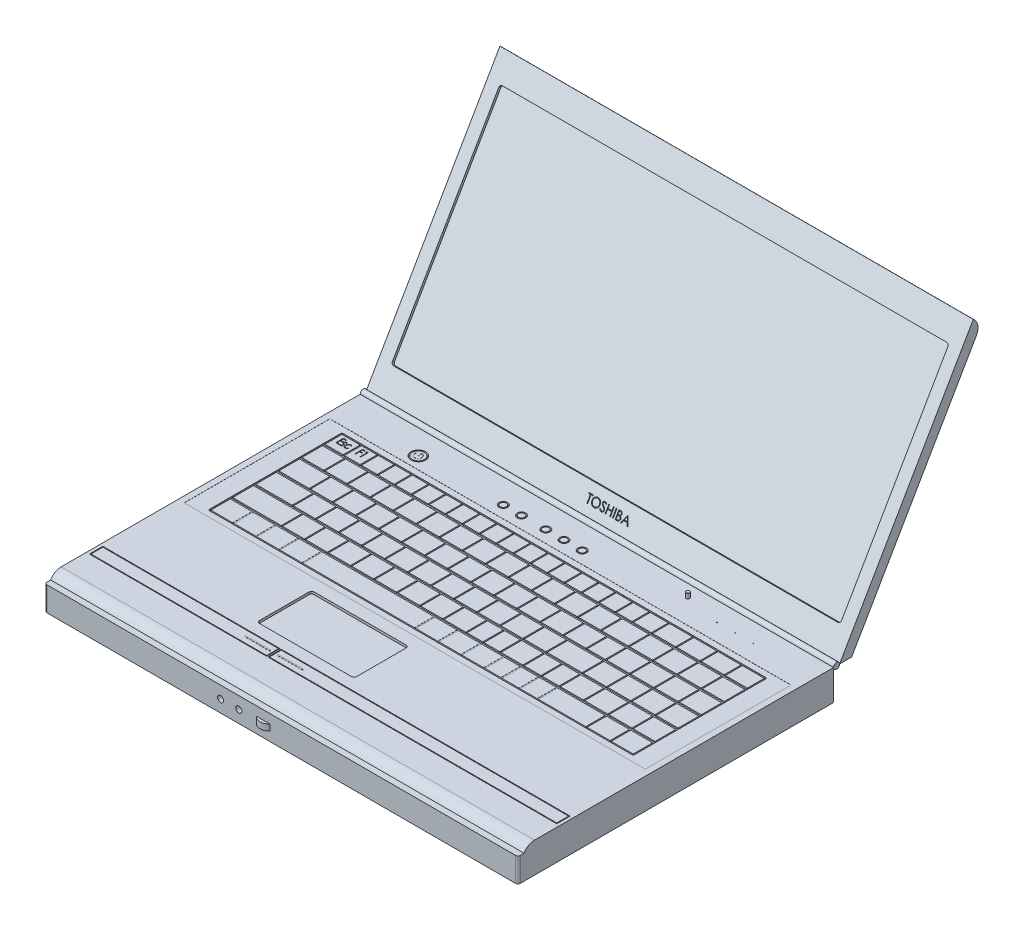
SolidWorks part; units mm, degrees
ref_plane "Front" through (0, 0, 0) normal (0, 0, 1) x (1, 0, 0)
ref_plane "Top" through (0, 0, 0) normal (0, 1, 0) x (1, 0, 0)
ref_plane "Right" through (0, 0, 0) normal (1, 0, 0) x (0, 0, -1)
sketch "Sketch1" plane through (0, 0, 0) normal (0, 1, 0) x (1, 0, 0)
  line L1 (-195, -130) -> (195, -130)
  line L2 (-195, -130) -> (-195, 130)
  line L3 (-195, 130) -> (195, 130)
  line L4 (195, -130) -> (195, 130)
  line L5 (-195, -130) -> (195, 130) construction
  line L6 (-195, 130) -> (195, -130) construction
  point P0 (0, 0)
  dimension "D1" = 390
  dimension "D2" = 260
extrude "Extrude1" add sketch "Sketch1" along normal blind 25
sketch "Sketch2" plane through (195, 0, 0) normal (1, 0, 0) x (0, 0, -1)
  line L0 (135, 25) -> (245.1819, 215.8407)
  line L1 (245.1819, 215.8407) -> (255.1819, 215.8407)
  line L2 (255.1819, 215.8407) -> (145, 25)
  line L3 (145, 25) -> (135, 25)
  line L4 (-130, 25) -> (130, 25) construction
  dimension "D1" = 5
  dimension "D2" = 120
  dimension "D3" = 10
extrude "Extrude2" add sketch "Sketch2" against normal through all separate body
sketch "Sketch3" plane through (195, 0, 0) normal (1, 0, 0) x (0, 0, -1)
  line L0 (122.4808, 25) -> (146.9706, 25) construction
  line L1 (-130, 25) -> (130, 25) construction
  line L2 (130, 25) -> (130, 0) construction
  circle A0 centre (132.5, 25) radius 2.5
  dimension "D1" = 5
extrude "Extrude3" add sketch "Sketch3" against normal through all separate body
sketch "Sketch4" plane through (0, -52.2067, -90.4247) normal (0, 0.5, 0.866) x (1, 0, 0)
  line L0 (-195, 309.5145) -> (-195, 89.1506) construction
  line L1 (-185, 110.4006) -> (185, 110.4006)
  line L2 (-185, 110.4006) -> (-185, 289.5145)
  line L3 (-185, 289.5145) -> (185, 289.5145)
  line L4 (185, 110.4006) -> (185, 289.5145)
  line L5 (-185, 110.4006) -> (185, 289.5145) construction
  line L6 (-185, 289.5145) -> (185, 110.4006) construction
  line L7 (195, 309.5145) -> (195, 89.1506) construction
  line L8 (-195, 309.5145) -> (195, 309.5145) construction
  line L9 (195, 90.4006) -> (-195, 90.4006) construction
  point P0 (0, 199.9576)
  dimension "D1" = 10
  dimension "D2" = 10
  dimension "D3" = 20
  dimension "D4" = 20
extrude "Extrude4" cut sketch "Sketch4" against normal blind 2
fillet "Fillet1" radius 2 4 edges at (185, 198.0202, -236.048) (185, 42.903, -146.491) (-185, 42.903, -146.491) (-185, 198.0202, -236.048)
fillet "Fillet2" radius 10 1 edges at (0, 215.8407, -255.1819)
sketch "Sketch5" plane through (0, 25, 0) normal (0, 1, 0) x (1, 0, 0)
  line L0 (195, -130) -> (195, 130) construction
  line L1 (-195, -130) -> (195, -130)
  line L2 (-195, -130) -> (-195, -125)
  line L3 (-195, -125) -> (195, -125)
  line L4 (195, -130) -> (195, -125)
  dimension "D1" = 5
extrude "Extrude5" cut sketch "Sketch5" against normal blind 5
fillet "Fillet3" radius 10 1 edges at (0, 25, 125)
fillet "Fillet4" radius 2 2 edges at (195, 10, 130) (-195, 10, 130)
sketch "Sketch6" plane through (0, 25, 0) normal (0, 1, 0) x (1, 0, 0)
  line L0 (-195, 130) -> (195, 130) construction
  line L1 (-75, -30) -> (5, -30)
  line L2 (-75, -30) -> (-75, -75)
  line L3 (-75, -75) -> (5, -75)
  line L4 (5, -30) -> (5, -75)
  line L5 (-195, 130) -> (-195, -116.3397) construction
  line L6 (-193, -130) -> (193, -130) construction
  circle A0 centre (-127.0409, 110) radius 6
  circle A1 centre (-127.0409, 110) radius 5
  circle A2 centre (-57.0409, 110) radius 3.5
  circle A3 centre (-57.0409, 110) radius 2.5
  circle A4 centre (-42.0409, 110) radius 3.5
  circle A5 centre (-42.0409, 110) radius 2.5
  circle A6 centre (-22.0409, 110) radius 3.5
  circle A7 centre (-22.0409, 110) radius 2.5
  circle A8 centre (-7.0409, 110) radius 3.5
  circle A9 centre (-7.0409, 110) radius 2.5
  circle A10 centre (7.9591, 110) radius 3.5
  circle A11 centre (7.9591, 110) radius 2.5
  dimension "D2" = 12
  dimension "D3" = 10
  dimension "D8" = 7
  dimension "D9" = 5
  dimension "D10" = 7
  dimension "D11" = 5
  dimension "D12" = 7
  dimension "D13" = 5
  dimension "D14" = 5
  dimension "D15" = 7
  dimension "D21" = 5
  dimension "D22" = 7
  dimension "D1" = 20
  dimension "D4" = 80
  dimension "D5" = 45
  dimension "D6" = 120
  dimension "D7" = 55
  dimension "D16" = 15
  dimension "D17" = 70
  dimension "D18" = 20
  dimension "D19" = 15
  dimension "D20" = 15
extrude "Extrude6" cut sketch "Sketch6" against normal blind 2
fillet "Fillet5" radius 2 4 edges at (5, 24, 30) (5, 24, 75) (-75, 24, 75) (-75, 24, 30)
sketch "Sketch8" plane through (0, 0, 130) normal (0, 0, 1) x (1, 0, 0)
  line L0 (-195, 0) -> (-195, 20) construction
  line L1 (-207.7397, 10) -> (97.3758, 10) construction
  line L2 (-193, 0) -> (193, 0) construction
  line L3 (-193, 20) -> (193, 20) construction
  circle A0 centre (-50, 10) radius 2.5
  circle A1 centre (-35, 10) radius 2.5
  dimension "D1" = 5
  dimension "D2" = 5
  dimension "D3" = 145
  dimension "D4" = 15
extrude "Extrude7" cut sketch "Sketch8" against normal blind 10
sketch "Sketch9" plane through (0, 25, 0) normal (0, 1, 0) x (1, 0, 0)
  line L0 (-195, 130) -> (195, 130) construction
  line L1 (195, -116.3397) -> (195, 130) construction
  circle A0 centre (85, 120) radius 1.5
  dimension "D1" = 3
  dimension "D2" = 10
  dimension "D3" = 110
extrude "Extrude8" add sketch "Sketch9" along normal blind 4
ref_plane "Plane1" through (0, 10, 0) normal (0, 1, 0) x (-1, 0, 0)
sketch "Sketch10" plane through (0, 10, 0) normal (0, 1, 0) x (-1, 0, 0)
  line L0 (-195, 125) -> (195, 125) construction
  line L1 (-195, 116.3397) -> (-195, -130) construction
  circle A0 centre (15, 125) radius 7.5
  dimension "D1" = 15
  dimension "D2" = 210
extrude "Extrude9" add sketch "Sketch10" along normal blind 2.5 and the other way blind 2.5
sketch "Sketch11" plane through (0, 25, 0) normal (0, 1, 0) x (1, 0, 0)
  line L1 (-192, -85) -> (-47, -85)
  line L2 (-192, -85) -> (-192, -95)
  line L3 (-192, -95) -> (-47, -95)
  line L4 (-47, -85) -> (-47, -95)
  line L5 (195, -116.3397) -> (195, 130) construction
  line L6 (-45, -95) -> (192, -95)
  line L7 (-45, -95) -> (-45, -85)
  line L8 (-45, -85) -> (192, -85)
  line L9 (-195, 130) -> (-195, -116.3397) construction
  line L10 (192, -95) -> (192, -85)
  line L11 (-193, -130) -> (193, -130) construction
  dimension "D1" = 3
  dimension "D2" = 3
  dimension "D3" = 2
  dimension "D4" = 10
  dimension "D5" = 35
  dimension "D6" = 145
sketch "Sketch14" plane through (0, 25, 0) normal (0, 1, 0) x (-1, 0, 0)
  line L0 (192, 85) -> (47, 85) construction
  line L1 (192.5, 84.5) -> (46.5, 84.5)
  line L2 (192.5, 84.5) -> (192.5, 95.5)
  line L3 (192.5, 95.5) -> (46.5, 95.5)
  line L4 (46.5, 84.5) -> (46.5, 95.5)
  line L5 (45.5, 95.5) -> (-192.5, 95.5)
  line L6 (45.5, 95.5) -> (45.5, 84.5)
  line L7 (45.5, 84.5) -> (-192.5, 84.5)
  line L8 (-192.5, 95.5) -> (-192.5, 84.5)
  line L9 (192, 95) -> (47, 95) construction
  line L10 (192, 85) -> (192, 95) construction
  line L11 (47, 85) -> (47, 95) construction
  line L12 (45, 95) -> (45, 85) construction
  line L13 (45, 95) -> (-192, 95) construction
  line L14 (45, 85) -> (-192, 85) construction
  line L15 (-192, 95) -> (-192, 85) construction
  dimension "D1" = 0.5
  dimension "D2" = 0.5
  dimension "D3" = 0.5
  dimension "D4" = 0.5
  dimension "D5" = 0.5
  dimension "D6" = 0.5
  dimension "D7" = 0.5
  dimension "D8" = 0.5
extrude "Extrude12" cut sketch "Sketch14" against normal blind 2
extrude "Extrude13" add sketch "Sketch11" against normal blind 2
sketch "Sketch15" plane through (0, 25, 0) normal (0, 1, 0) x (1, 0, 0)
  line L0 (-69.5, -90) -> (-49.5, -90) construction
  line L1 (-69.5, -89.5) -> (-49.5, -89.5)
  line L2 (-69.5, -90.5) -> (-49.5, -90.5)
  line L3 (-42.5, -90) -> (-22.5, -90) construction
  line L4 (-42.5, -89.5) -> (-22.5, -89.5)
  line L5 (-42.5, -90.5) -> (-22.5, -90.5)
  line L6 (-47, -85) -> (-192, -85) construction
  line L7 (-192, -95) -> (-47, -95) construction
  line L9 (-47, -95) -> (-47, -85) construction
  line L10 (-45, -85) -> (-45, -95) construction
  arc A0 (-69.5, -89.5) -> (-69.5, -90.5) centre (-69.5, -90) ccw
  arc A1 (-49.5, -90.5) -> (-49.5, -89.5) centre (-49.5, -90) ccw
  arc A2 (-42.5, -89.5) -> (-42.5, -90.5) centre (-42.5, -90) ccw
  arc A3 (-22.5, -90.5) -> (-22.5, -89.5) centre (-22.5, -90) ccw
  point P2 (-59.5, -90)
  point P7 (-32.5, -90)
  point P20 (-45, -90)
  dimension "D1" = 1
  dimension "D2" = 1
  dimension "D3" = 20
  dimension "D4" = 20
  dimension "D5" = 2.5
  dimension "D6" = 2.5
extrude "Extrude14" add sketch "Sketch15" along normal blind 0.1
chamfer "Chamfer1" distance 0.1 angle 45 8 edges at (192, 25, 90) (73.5, 25, 95) (-45, 25, 90) (73.5, 25, 85) (-192, 25, 90) (-119.5, 25, 85) (-47, 25, 90) (-119.5, 25, 95)
sketch "Sketch16" plane through (0, 25, 0) normal (0, 1, 0) x (1, 0, 0)
  line L0 (-195, 130) -> (-195, -116.3397) construction
  line L1 (-190, 100) -> (190, 100)
  line L2 (-190, 100) -> (-190, -20)
  line L3 (-190, -20) -> (190, -20)
  line L4 (190, 100) -> (190, -20)
  line L5 (195, -116.3397) -> (195, 130) construction
  line L6 (195, 130) -> (-195, 130) construction
  dimension "D1" = 5
  dimension "D2" = 5
  dimension "D3" = 30
  dimension "D4" = 120
extrude "Extrude15" cut sketch "Sketch16" against normal blind 0.1
sketch "Sketch17" plane through (0, 25, 0) normal (0, 1, 0) x (1, 0, 0)
  line L0 (-127.1409, 103.668) -> (-127.1409, 116.8191) construction
  line L1 (-127.2409, 114) -> (-127.0409, 114)
  line L2 (-127.2409, 114) -> (-127.2409, 110)
  line L3 (-127.2409, 110) -> (-127.0409, 110)
  line L4 (-127.0409, 114) -> (-127.0409, 110)
  line L5 (-126.0409, 112.7911) -> (-126.0409, 112.5749)
  line L6 (-128.2409, 112.7911) -> (-128.2409, 112.5749)
  circle A0 centre (-127.0409, 110) radius 5 construction
  circle A3 centre (-127.0409, 110) radius 5 construction
  arc A4 (-126.0409, 112.7911) -> (-128.2409, 112.7911) centre (-127.1409, 110) cw
  arc A5 (-126.0409, 112.5749) -> (-128.2409, 112.5749) centre (-127.1409, 110) cw
  dimension "D7" = 2.8
  dimension "D8" = 3
  dimension "D1" = 4
  dimension "D2" = 0.2
  dimension "D3" = 0
  dimension "D4" = 0
  dimension "D5" = 1
  dimension "D6" = 1
extrude "Extrude16" cut sketch "Sketch17" against normal blind 0.1
sketch "Sketch18" plane through (0, 24.9, 0) normal (0, 1, 0) x (1, 0, 0)
  line L0 (190, 100) -> (-190, 100) construction
  line L1 (-175, 95) -> (175, 95)
  line L2 (-175, 95) -> (-175, -15)
  line L3 (-175, -15) -> (175, -15)
  line L4 (175, 95) -> (175, -15)
  line L5 (-190, 100) -> (-190, -20) construction
  line L6 (-190, -20) -> (190, -20) construction
  line L7 (190, -20) -> (190, 100) construction
  dimension "D1" = 5
  dimension "D2" = 15
  dimension "D3" = 5
  dimension "D4" = 15
extrude "Extrude17" cut sketch "Sketch18" against normal blind 0.1
fillet "Fillet6" radius 1 4 edges at (175, 24.85, -95) (175, 24.85, 15) (-175, 24.85, 15) (-175, 24.85, -95)
chamfer "Chamfer2" distance 0.1 angle 45 8 edges at (0, 24.9, 15) (174.7071, 24.9, 14.7071) (-174.7071, 24.9, 14.7071) (175, 24.9, -40) (-175, 24.9, -40) (174.7071, 24.9, -94.7071) (-174.7071, 24.9, -94.7071) (0, 24.9, -95)
sketch "Sketch19" plane through (0, 24.8, 0) normal (0, 1, 0) x (1, 0, 0)
  line L0 (-174.1, 61) -> (95.9, 61)
  line L2 (-174.1, 59) -> (95.9, 59)
  line L3 (95.9, 21) -> (-174.1, 21)
  line L5 (-174.1, 21) -> (-174.1, 23)
  line L6 (-174.1, 4) -> (-174.1, 2)
  line L7 (-174.1, 2) -> (95.9, 2)
  line L8 (-174, -15) -> (174, -15) construction
  line L9 (-174.1, 40) -> (-174.1, 42)
  line L10 (-174.1, 80) -> (-174.1, 78)
  line L11 (-174.1, 61) -> (-174.1, 59)
  line L12 (-175.1, -14) -> (-175.1, 94) construction
  line L19 (95.9, 61) -> (95.9, 59)
  line L20 (-174.1, 80) -> (95.9, 80)
  line L21 (-174.1, 78) -> (95.9, 78)
  line L22 (95.9, 80) -> (95.9, 78)
  line L35 (-174.1, 42) -> (95.9, 42)
  line L37 (-174.1, 40) -> (95.9, 40)
  line L38 (95.9, 42) -> (95.9, 40)
  line L39 (-174.1, 23) -> (95.9, 23)
  line L42 (95.9, 23) -> (95.9, 21)
  line L43 (-174.1, 4) -> (95.9, 4)
  line L46 (95.9, 4) -> (95.9, 2)
  dimension "D2" = 2
  dimension "D3" = 17
  dimension "D4" = 2
  dimension "D5" = 270
  dimension "D6" = 17
  dimension "D7" = 2
  dimension "D8" = 2
  dimension "D9" = 2
  dimension "D10" = 17
  dimension "D11" = 17
  dimension "D12" = 17
  dimension "D13" = 1
extrude "Extrude18" cut sketch "Sketch19" against normal blind 1
sketch "Sketch20" plane through (0, 24.8, 0) normal (0, 1, 0) x (-1, 0, 0)
  line L0 (175, -94) -> (175, 14)
  line L1 (174, -94) -> (175, -94)
  line L2 (174, -94) -> (174, 14)
  line L3 (175, 14) -> (174, 14)
extrude "Extrude19" cut sketch "Sketch20" against normal blind 1
sketch "Sketch23" plane through (0, 24.8, 0) normal (0, 1, 0) x (1, 0, 0)
  line L0 (-174, -14) -> (-174, -15)
  line L1 (-175, -14) -> (-174, -14)
  arc A0 (-174, -15) -> (-175, -14) centre (-174, -14) cw
extrude "Extrude24" cut sketch "Sketch23" against normal blind 1
sketch "Sketch25" plane through (0, 24.8, 0) normal (0, 1, 0) x (1, 0, 0)
  line L0 (-174, 94) -> (-174, 95)
  line L1 (174, 95) -> (-174, 95) construction
  line L2 (-175, 94) -> (-174, 94)
  arc A0 (-174, 95) -> (-175, 94) centre (-174, 94) ccw construction
  arc A1 (-174, 95) -> (-175, 94) centre (-174, 94) ccw
extrude "Extrude25" cut sketch "Sketch25" against normal blind 1
sketch "Sketch26" plane through (0, 24.8, 0) normal (0, 1, 0) x (-1, 0, 0)
  line L1 (174, -95) -> (-174, -95)
  line L2 (174, -95) -> (174, -94)
  line L3 (174, -94) -> (-174, -94)
  line L4 (-174, -95) -> (-174, -94)
extrude "Extrude26" cut sketch "Sketch26" against normal blind 1
sketch "Sketch27" plane through (0, 24.8, 0) normal (0, 1, 0) x (-1, 0, 0)
  line L0 (-174, -95) -> (-174, -94)
  line L1 (-174, -94) -> (-175, -94)
  arc A0 (-175, -94) -> (-174, -95) centre (-174, -94) ccw
extrude "Extrude27" cut sketch "Sketch27" against normal blind 1
sketch "Sketch28" plane through (0, 24.8, 0) normal (0, 1, 0) x (1, 0, 0)
  line L1 (175, 94) -> (174, 94)
  line L2 (175, 94) -> (175, -14)
  line L3 (175, -14) -> (174, -14)
  line L4 (174, 94) -> (174, -14)
extrude "Extrude28" cut sketch "Sketch28" against normal blind 1
sketch "Sketch29" plane through (0, 24.8, 0) normal (0, 1, 0) x (-1, 0, 0)
  line L0 (-174, 14) -> (-174, 15)
  line L1 (-175, 14) -> (-174, 14)
  arc A0 (-174, 15) -> (-175, 14) centre (-174, 14) ccw
extrude "Extrude29" cut sketch "Sketch29" against normal blind 1
sketch "Sketch30" plane through (0, 24.8, 0) normal (0, 1, 0) x (-1, 0, 0)
  line L1 (-174, 15) -> (174, 15)
  line L2 (-174, 15) -> (-174, 14)
  line L3 (-174, 14) -> (174, 14)
  line L4 (174, 15) -> (174, 14)
extrude "Extrude30" cut sketch "Sketch30" against normal blind 1
sketch "Sketch31" plane through (0, 24.8, 0) normal (0, 1, 0) x (1, 0, 0)
  line L0 (-174, 94) -> (174, 94) construction
  line L1 (-159, 94) -> (-158, 94)
  line L2 (-159, 94) -> (-159, 80)
  line L3 (-159, 80) -> (-158, 80)
  line L4 (-158, 94) -> (-158, 80)
  line L5 (95.9, 80) -> (-174, 80) construction
  line L6 (95.9, 80) -> (-174, 80) construction
  line L7 (-145, 94) -> (-144, 94)
  line L8 (-145, 94) -> (-145, 80)
  line L9 (-145, 80) -> (-144, 80)
  line L10 (-144, 94) -> (-144, 80)
  line L11 (-174, 94) -> (174, 94) construction
  line L12 (-131, 94) -> (-130, 94)
  line L13 (-131, 94) -> (-131, 80)
  line L14 (-131, 80) -> (-130, 80)
  line L15 (-130, 94) -> (-130, 80)
  line L16 (-174, 80) -> (-174, 94) construction
  line L17 (-117, 94) -> (-116, 94)
  line L18 (-117, 94) -> (-117, 80)
  line L19 (-117, 80) -> (-116, 80)
  line L20 (-116, 94) -> (-116, 80)
  dimension "D1" = 1
  dimension "D2" = 1
  dimension "D3" = 1
  dimension "D4" = 1
  dimension "D5" = 15
  dimension "D6" = 13
  dimension "D7" = 13
  dimension "D8" = 13
extrude "Extrude31" cut sketch "Sketch31" against normal blind 1
sketch "Sketch32" plane through (0, 24.8, 0) normal (0, 1, 0) x (1, 0, 0)
  line L0 (-116, 94) -> (174, 94) construction
  line L1 (-103, 94) -> (-102, 94)
  line L2 (-103, 94) -> (-103, 80)
  line L3 (-103, 80) -> (-102, 80)
  line L4 (-102, 94) -> (-102, 80)
  line L5 (95.9, 80) -> (-116, 80) construction
  line L7 (-89, 94) -> (-88, 94)
  line L8 (-89, 94) -> (-89, 80)
  line L9 (-89, 80) -> (-88, 80)
  line L10 (-88, 94) -> (-88, 80)
  line L11 (-75, 94) -> (-74, 94)
  line L12 (-75, 94) -> (-75, 80)
  line L13 (-75, 80) -> (-74, 80)
  line L14 (-74, 94) -> (-74, 80)
  line L15 (-61, 94) -> (-60, 94)
  line L16 (-61, 94) -> (-61, 80)
  line L17 (-61, 80) -> (-60, 80)
  line L18 (-60, 94) -> (-60, 80)
  line L19 (-116, 80) -> (-116, 94) construction
  line L20 (-47, 94) -> (-46, 94)
  line L21 (-47, 94) -> (-47, 80)
  line L22 (-47, 80) -> (-46, 80)
  line L23 (-116, 94) -> (174, 94) construction
  line L24 (-33, 94) -> (-32, 94)
  line L25 (-33, 94) -> (-33, 80)
  line L26 (-33, 80) -> (-32, 80)
  line L27 (-32, 94) -> (-32, 80)
  line L28 (95.9, 80) -> (-116, 80) construction
  line L29 (-46, 94) -> (-46, 80)
  line L30 (-19, 94) -> (-18, 94)
  line L31 (-19, 94) -> (-19, 80)
  line L32 (-19, 80) -> (-18, 80)
  line L33 (-18, 94) -> (-18, 80)
  line L34 (9, 94) -> (10, 94)
  line L35 (9, 94) -> (9, 80)
  line L36 (9, 80) -> (10, 80)
  line L37 (10, 94) -> (10, 80)
  line L38 (-5, 94) -> (-4, 94)
  line L39 (-5, 94) -> (-5, 80)
  line L40 (-5, 80) -> (-4, 80)
  line L41 (-4, 94) -> (-4, 80)
  dimension "D1" = 1
  dimension "D2" = 1
  dimension "D3" = 1
  dimension "D4" = 1
  dimension "D5" = 1
  dimension "D6" = 1
  dimension "D7" = 1
  dimension "D8" = 1
  dimension "D9" = 1
  dimension "D10" = 13
  dimension "D11" = 13
  dimension "D12" = 13
  dimension "D13" = 13
  dimension "D14" = 13
  dimension "D15" = 13
  dimension "D16" = 13
  dimension "D17" = 13
  dimension "D18" = 13
extrude "Extrude32" cut sketch "Sketch32" against normal blind 1
sketch "Sketch33" plane through (0, 24.8, 0) normal (0, 1, 0) x (1, 0, 0)
  line L0 (10, 94) -> (174, 94) construction
  line L1 (23, 94) -> (24, 94)
  line L2 (23, 94) -> (23, 80)
  line L3 (23, 80) -> (24, 80)
  line L4 (24, 94) -> (24, 80)
  line L5 (95.9, 80) -> (10, 80) construction
  line L6 (10, 94) -> (174, 94) construction
  line L7 (37, 94) -> (38, 94)
  line L8 (37, 94) -> (37, 80)
  line L9 (37, 80) -> (38, 80)
  line L10 (38, 94) -> (38, 80)
  line L11 (10, 80) -> (10, 94) construction
  line L12 (51, 94) -> (52, 94)
  line L13 (51, 94) -> (51, 80)
  line L14 (51, 80) -> (52, 80)
  line L15 (52, 94) -> (52, 80)
  line L16 (65, 94) -> (66, 94)
  line L17 (65, 94) -> (65, 80)
  line L18 (65, 80) -> (66, 80)
  line L19 (66, 94) -> (66, 80)
  line L20 (79, 94) -> (80, 94)
  line L21 (79, 94) -> (79, 80)
  line L22 (79, 80) -> (80, 80)
  line L23 (80, 94) -> (80, 80)
  line L24 (94.9, 94) -> (95.9, 94)
  line L25 (94.9, 94) -> (94.9, 80)
  line L26 (94.9, 80) -> (95.9, 80)
  line L27 (95.9, 94) -> (95.9, 80)
  line L28 (95.9, 78) -> (95.9, 80) construction
  line L29 (95.9, 80) -> (10, 80) construction
  dimension "D1" = 1
  dimension "D2" = 1
  dimension "D3" = 1
  dimension "D4" = 1
  dimension "D5" = 1
  dimension "D6" = 1
  dimension "D7" = 13
  dimension "D8" = 13
  dimension "D9" = 13
  dimension "D10" = 13
  dimension "D11" = 13
extrude "Extrude33" cut sketch "Sketch33" against normal blind 1
sketch "Sketch34" plane through (0, 25, 0) normal (0, 1, 0) x (1, 0, 0)
  text T1 "Esc" font "Century Gothic" height 6.35
extrude "Extrude37" cut sketch "Sketch34" against normal blind 1
sketch "Sketch35" plane through (0, 24.8, 0) normal (0, 1, 0) x (1, 0, 0)
  text T0 "F1" font "Century Gothic" height 6.35
extrude "Extrude38" cut sketch "Sketch35" against normal blind 1
sketch "Sketch36" plane through (0, 24.8, 0) normal (0, 1, 0) x (1, 0, 0)
  line L0 (-174, 78) -> (95.9, 78) construction
  line L1 (-156, 78) -> (-155, 78)
  line L2 (-156, 78) -> (-156, 61)
  line L3 (-156, 61) -> (-155, 61)
  line L4 (-155, 78) -> (-155, 61)
  line L5 (95.9, 61) -> (-174, 61) construction
  line L6 (95.9, 61) -> (-174, 61) construction
  line L7 (-137, 78) -> (-136, 78)
  line L8 (-137, 78) -> (-137, 61)
  line L9 (-137, 61) -> (-136, 61)
  line L10 (-136, 78) -> (-136, 61)
  line L11 (-118, 78) -> (-117, 78)
  line L12 (-118, 78) -> (-118, 61)
  line L13 (-118, 61) -> (-117, 61)
  line L14 (-117, 78) -> (-117, 61)
  line L15 (-99, 78) -> (-98, 78)
  line L16 (-99, 78) -> (-99, 61)
  line L17 (-99, 61) -> (-98, 61)
  line L18 (-98, 78) -> (-98, 61)
  line L19 (-80, 78) -> (-79, 78)
  line L20 (-80, 78) -> (-80, 61)
  line L21 (-80, 61) -> (-79, 61)
  line L22 (-79, 78) -> (-79, 61)
  line L23 (-61, 78) -> (-60, 78)
  line L24 (-61, 78) -> (-61, 61)
  line L25 (-61, 61) -> (-60, 61)
  line L26 (-60, 78) -> (-60, 61)
  line L27 (-42, 78) -> (-41, 78)
  line L28 (-42, 78) -> (-42, 61)
  line L29 (-42, 61) -> (-41, 61)
  line L30 (-41, 78) -> (-41, 61)
  line L31 (-23, 78) -> (-22, 78)
  line L32 (-23, 78) -> (-23, 61)
  line L33 (-23, 61) -> (-22, 61)
  line L34 (-22, 78) -> (-22, 61)
  line L35 (-4, 78) -> (-3, 78)
  line L36 (-4, 78) -> (-4, 61)
  line L37 (-4, 61) -> (-3, 61)
  line L38 (-3, 78) -> (-3, 61)
  line L39 (-174, 78) -> (95.9, 78) construction
  line L40 (15, 78) -> (16, 78)
  line L41 (15, 78) -> (15, 61)
  line L42 (15, 61) -> (16, 61)
  line L43 (16, 78) -> (16, 61)
  line L44 (34, 78) -> (35, 78)
  line L45 (34, 78) -> (34, 61)
  line L46 (34, 61) -> (35, 61)
  line L47 (35, 78) -> (35, 61)
  line L49 (-174, 61) -> (-174, 78) construction
  line L51 (95.9, 78) -> (94.9, 78)
  line L52 (53, 78) -> (54, 78)
  line L53 (53, 78) -> (53, 61)
  line L54 (53, 61) -> (54, 61)
  line L55 (54, 78) -> (54, 61)
  line L56 (72, 78) -> (73, 78)
  line L57 (72, 78) -> (72, 61)
  line L58 (72, 61) -> (73, 61)
  line L59 (73, 78) -> (73, 61)
  line L60 (95.9, 78) -> (95.9, 61)
  line L61 (95.9, 61) -> (94.9, 61)
  line L62 (94.9, 78) -> (94.9, 61)
  dimension "D1" = 1
  dimension "D2" = 1
  dimension "D3" = 1
  dimension "D4" = 1
  dimension "D5" = 1
  dimension "D6" = 1
  dimension "D7" = 1
  dimension "D8" = 1
  dimension "D9" = 1
  dimension "D10" = 1
  dimension "D11" = 1
  dimension "D12" = 1
  dimension "D13" = 1
  dimension "D14" = 18
  dimension "D15" = 18
  dimension "D16" = 18
  dimension "D17" = 18
  dimension "D18" = 18
  dimension "D19" = 18
  dimension "D20" = 18
  dimension "D21" = 18
  dimension "D22" = 18
  dimension "D23" = 18
  dimension "D24" = 18
  dimension "D25" = 18
  dimension "D26" = 18
  dimension "D27" = 1
extrude "Extrude39" cut sketch "Sketch36" against normal blind 1
sketch "Sketch37" plane through (0, 24.8, 0) normal (0, 1, 0) x (1, 0, 0)
  line L0 (-174, 59) -> (95.9, 59) construction
  line L1 (-149, 59) -> (-148, 59)
  line L2 (-149, 59) -> (-149, 42)
  line L3 (-149, 42) -> (-148, 42)
  line L4 (-148, 59) -> (-148, 42)
  line L5 (95.9, 42) -> (-174, 42) construction
  line L6 (-174, 42) -> (-174, 59) construction
  dimension "D1" = 1
  dimension "D2" = 25
extrude "Extrude40" cut sketch "Sketch37" against normal blind 1
sketch "Sketch38" plane through (0, 24.8, 0) normal (0, 1, 0) x (-1, 0, 0)
  line L0 (148, -59) -> (-95.9, -59) construction
  line L1 (130, -59) -> (129, -59)
  line L2 (130, -59) -> (130, -42)
  line L3 (130, -42) -> (129, -42)
  line L4 (129, -59) -> (129, -42)
  line L5 (-95.9, -42) -> (148, -42) construction
  line L6 (-95.9, -42) -> (148, -42) construction
  line L7 (111, -59) -> (110, -59)
  line L8 (111, -59) -> (111, -42)
  line L9 (111, -42) -> (110, -42)
  line L10 (110, -59) -> (110, -42)
  line L11 (92, -59) -> (91, -59)
  line L12 (92, -59) -> (92, -42)
  line L13 (92, -42) -> (91, -42)
  line L14 (91, -59) -> (91, -42)
  line L15 (148, -59) -> (-95.9, -59) construction
  line L16 (73, -59) -> (72, -59)
  line L17 (73, -59) -> (73, -42)
  line L18 (73, -42) -> (72, -42)
  line L19 (72, -59) -> (72, -42)
  line L21 (54, -59) -> (53, -59)
  line L22 (54, -59) -> (54, -42)
  line L23 (54, -42) -> (53, -42)
  line L24 (53, -59) -> (53, -42)
  line L25 (35, -59) -> (34, -59)
  line L26 (35, -59) -> (35, -42)
  line L27 (35, -42) -> (34, -42)
  line L28 (34, -59) -> (34, -42)
  line L29 (16, -59) -> (15, -59)
  line L30 (16, -59) -> (16, -42)
  line L31 (16, -42) -> (15, -42)
  line L32 (15, -59) -> (15, -42)
  line L33 (-3, -59) -> (-4, -59)
  line L34 (-3, -59) -> (-3, -42)
  line L35 (-3, -42) -> (-4, -42)
  line L36 (-4, -59) -> (-4, -42)
  line L37 (148, -42) -> (148, -59) construction
  line L38 (-95.9, -40) -> (-95.9, -42) construction
  line L39 (-95.9, -59) -> (-94.9, -59)
  line L40 (-95.9, -59) -> (-95.9, -42)
  line L41 (-95.9, -42) -> (-94.9, -42)
  line L42 (-94.9, -59) -> (-94.9, -42)
  line L43 (-80, -59) -> (-79, -59)
  line L44 (-80, -59) -> (-80, -42)
  line L45 (-80, -42) -> (-79, -42)
  line L46 (-79, -59) -> (-79, -42)
  line L47 (-61, -59) -> (-60, -59)
  line L48 (-61, -59) -> (-61, -42)
  line L49 (-61, -42) -> (-60, -42)
  line L50 (-60, -59) -> (-60, -42)
  line L51 (-42, -59) -> (-41, -59)
  line L52 (-42, -59) -> (-42, -42)
  line L53 (-42, -42) -> (-41, -42)
  line L54 (-41, -59) -> (-41, -42)
  line L55 (-23, -59) -> (-22, -59)
  line L56 (-23, -59) -> (-23, -42)
  line L57 (-23, -42) -> (-22, -42)
  line L58 (-22, -59) -> (-22, -42)
  dimension "D1" = 1
  dimension "D2" = 1
  dimension "D3" = 18
  dimension "D4" = 1
  dimension "D5" = 1
  dimension "D6" = 1
  dimension "D7" = 1
  dimension "D8" = 1
  dimension "D9" = 1
  dimension "D10" = 18
  dimension "D11" = 18
  dimension "D12" = 18
  dimension "D13" = 1
  dimension "D14" = 1
  dimension "D15" = 1
  dimension "D16" = 1
  dimension "D17" = 1
  dimension "D18" = 18
  dimension "D19" = 18
  dimension "D20" = 18
  dimension "D21" = 18
  dimension "D22" = 18
  dimension "D23" = 18
  dimension "D24" = 18
  dimension "D25" = 18
extrude "Extrude41" cut sketch "Sketch38" against normal up to vertex (1 mm away) up to point (95.9, 23.8, -40)
sketch "Sketch39" plane through (0, 24.8, 0) normal (0, 1, 0) x (1, 0, 0)
  line L0 (-174, 40) -> (95.9, 40) construction
  line L1 (-144, 40) -> (-143, 40)
  line L2 (-144, 40) -> (-144, 23)
  line L3 (-144, 23) -> (-143, 23)
  line L4 (-143, 40) -> (-143, 23)
  line L5 (95.9, 23) -> (-174, 23) construction
  line L6 (-174, 40) -> (95.9, 40) construction
  line L7 (-125, 40) -> (-124, 40)
  line L8 (-125, 40) -> (-125, 23)
  line L9 (-125, 23) -> (-124, 23)
  line L10 (-124, 40) -> (-124, 23)
  line L11 (95.9, 23) -> (-174, 23) construction
  line L12 (-106, 40) -> (-105, 40)
  line L13 (-106, 40) -> (-106, 23)
  line L14 (-106, 23) -> (-105, 23)
  line L15 (-105, 40) -> (-105, 23)
  line L17 (-87, 40) -> (-86, 40)
  line L18 (-87, 40) -> (-87, 23)
  line L19 (-87, 23) -> (-86, 23)
  line L20 (-86, 40) -> (-86, 23)
  line L21 (-68, 40) -> (-67, 40)
  line L22 (-68, 40) -> (-68, 23)
  line L23 (-68, 23) -> (-67, 23)
  line L24 (-67, 40) -> (-67, 23)
  line L25 (-49, 40) -> (-48, 40)
  line L26 (-49, 40) -> (-49, 23)
  line L27 (-49, 23) -> (-48, 23)
  line L28 (-48, 40) -> (-48, 23)
  line L29 (-30, 40) -> (-29, 40)
  line L30 (-30, 40) -> (-30, 23)
  line L31 (-30, 23) -> (-29, 23)
  line L32 (-29, 40) -> (-29, 23)
  line L33 (-11, 40) -> (-10, 40)
  line L34 (-11, 40) -> (-11, 23)
  line L35 (-11, 23) -> (-10, 23)
  line L36 (-10, 40) -> (-10, 23)
  line L37 (-174, 23) -> (-174, 40) construction
  line L38 (8, 40) -> (9, 40)
  line L39 (8, 40) -> (8, 23)
  line L40 (8, 23) -> (9, 23)
  line L41 (9, 40) -> (9, 23)
  line L42 (27, 40) -> (28, 40)
  line L43 (27, 40) -> (27, 23)
  line L44 (27, 23) -> (28, 23)
  line L45 (28, 40) -> (28, 23)
  line L46 (46, 40) -> (47, 40)
  line L47 (46, 40) -> (46, 23)
  line L48 (46, 23) -> (47, 23)
  line L49 (47, 40) -> (47, 23)
  line L50 (65, 40) -> (66, 40)
  line L51 (65, 40) -> (65, 23)
  line L52 (65, 23) -> (66, 23)
  line L53 (66, 40) -> (66, 23)
  line L54 (95.9, 40) -> (94.9, 40)
  line L55 (95.9, 40) -> (95.9, 23)
  line L56 (95.9, 23) -> (94.9, 23)
  line L57 (94.9, 40) -> (94.9, 23)
  dimension "D1" = 1
  dimension "D2" = 1
  dimension "D3" = 1
  dimension "D4" = 1
  dimension "D5" = 1
  dimension "D6" = 1
  dimension "D7" = 1
  dimension "D8" = 1
  dimension "D9" = 1
  dimension "D10" = 1
  dimension "D11" = 1
  dimension "D12" = 1
  dimension "D13" = 30
  dimension "D14" = 18
  dimension "D15" = 18
  dimension "D16" = 18
  dimension "D17" = 18
  dimension "D18" = 18
  dimension "D19" = 18
  dimension "D20" = 18
  dimension "D21" = 18
  dimension "D22" = 18
  dimension "D23" = 18
  dimension "D24" = 18
  dimension "D25" = 1
extrude "Extrude42" cut sketch "Sketch39" against normal blind 1
sketch "Sketch40" plane through (0, 24.8, 0) normal (0, 1, 0) x (1, 0, 0)
  line L0 (-174, 21) -> (95.9, 21) construction
  line L1 (-134, 21) -> (-133, 21)
  line L2 (-134, 21) -> (-134, 4)
  line L3 (-134, 4) -> (-133, 4)
  line L4 (-133, 21) -> (-133, 4)
  line L5 (95.9, 4) -> (-174, 4) construction
  line L6 (-174, 21) -> (95.9, 21) construction
  line L7 (-115, 21) -> (-114, 21)
  line L8 (-115, 21) -> (-115, 4)
  line L9 (-115, 4) -> (-114, 4)
  line L10 (-114, 21) -> (-114, 4)
  line L11 (-96, 21) -> (-95, 21)
  line L12 (-96, 21) -> (-96, 4)
  line L13 (-96, 4) -> (-95, 4)
  line L14 (-95, 21) -> (-95, 4)
  line L15 (-77, 21) -> (-76, 21)
  line L16 (-77, 21) -> (-77, 4)
  line L17 (-77, 4) -> (-76, 4)
  line L18 (-76, 21) -> (-76, 4)
  line L19 (95.9, 4) -> (-174, 4) construction
  line L21 (-58, 21) -> (-57, 21)
  line L22 (-58, 21) -> (-58, 4)
  line L23 (-58, 4) -> (-57, 4)
  line L24 (-57, 21) -> (-57, 4)
  line L26 (-39, 21) -> (-38, 21)
  line L27 (-39, 21) -> (-39, 4)
  line L28 (-39, 4) -> (-38, 4)
  line L29 (-20, 21) -> (-19, 21)
  line L30 (-20, 21) -> (-20, 4)
  line L31 (-20, 4) -> (-19, 4)
  line L32 (-19, 21) -> (-19, 4)
  line L33 (-1, 21) -> (0, 21)
  line L34 (-1, 21) -> (-1, 4)
  line L35 (-1, 4) -> (0, 4)
  line L36 (0, 21) -> (0, 4)
  line L37 (-174, 4) -> (-174, 21) construction
  line L38 (18, 21) -> (19, 21)
  line L39 (18, 21) -> (18, 4)
  line L40 (18, 4) -> (19, 4)
  line L41 (19, 21) -> (19, 4)
  line L42 (32, 21) -> (33, 21)
  line L43 (32, 21) -> (32, 4)
  line L44 (32, 4) -> (33, 4)
  line L45 (33, 21) -> (33, 4)
  line L46 (46, 21) -> (47, 21)
  line L47 (46, 21) -> (46, 4)
  line L48 (46, 4) -> (47, 4)
  line L49 (47, 21) -> (47, 4)
  line L50 (65, 21) -> (66, 21)
  line L51 (65, 21) -> (65, 4)
  line L52 (65, 4) -> (66, 4)
  line L53 (66, 21) -> (66, 4)
  line L54 (80, 21) -> (81, 21)
  line L55 (80, 21) -> (80, 4)
  line L56 (80, 4) -> (81, 4)
  line L57 (81, 21) -> (81, 4)
  line L58 (-38, 21) -> (-38, 4)
  line L59 (95.9, 21) -> (94.9, 21)
  line L60 (95.9, 21) -> (95.9, 4)
  line L61 (95.9, 4) -> (94.9, 4)
  line L62 (94.9, 21) -> (94.9, 4)
  dimension "D1" = 1
  dimension "D2" = 1
  dimension "D3" = 1
  dimension "D4" = 1
  dimension "D5" = 1
  dimension "D6" = 1
  dimension "D7" = 1
  dimension "D8" = 1
  dimension "D9" = 1
  dimension "D10" = 1
  dimension "D11" = 1
  dimension "D12" = 1
  dimension "D13" = 1
  dimension "D14" = 40
  dimension "D15" = 18
  dimension "D16" = 18
  dimension "D17" = 18
  dimension "D18" = 18
  dimension "D19" = 18
  dimension "D20" = 18
  dimension "D21" = 18
  dimension "D22" = 18
  dimension "D23" = 18
  dimension "D24" = 13
  dimension "D25" = 13
  dimension "D26" = 14
  dimension "D27" = 1
extrude "Extrude43" cut sketch "Sketch40" against normal blind 1
sketch "Sketch41" plane through (0, 25, 0) normal (0, 1, 0) x (1, 0, 0)
  line L0 (195, -116.3397) -> (195, 130) construction
  line L1 (95.9, 94) -> (174, 94) construction
  circle A0 centre (115, 114) radius 0.5
  circle A1 centre (130, 114) radius 0.5
  circle A2 centre (145, 114) radius 0.5
  dimension "D1" = 1
  dimension "D2" = 1
  dimension "D3" = 1
  dimension "D4" = 15
  dimension "D5" = 15
  dimension "D6" = 50
  dimension "D7" = 20
extrude "Extrude44" cut sketch "Sketch41" against normal blind 0.1
sketch "Sketch42" plane through (0, 24.8, 0) normal (0, 1, 0) x (1, 0, 0)
  line L0 (-174, 2) -> (95.9, 2) construction
  line L1 (-156, 2) -> (-155, 2)
  line L2 (-156, 2) -> (-156, -14)
  line L3 (-156, -14) -> (-155, -14)
  line L4 (-155, 2) -> (-155, -14)
  line L5 (174, -14) -> (-174, -14) construction
  line L6 (-174, 2) -> (95.9, 2) construction
  line L7 (-137, 2) -> (-136, 2)
  line L8 (-137, 2) -> (-137, -14)
  line L9 (-137, -14) -> (-136, -14)
  line L10 (-136, 2) -> (-136, -14)
  line L11 (174, -14) -> (-174, -14) construction
  line L12 (-174, -14) -> (-174, 2) construction
  line L13 (-118, 2) -> (-117, 2)
  line L14 (-118, 2) -> (-118, -14)
  line L15 (-118, -14) -> (-117, -14)
  line L16 (-117, 2) -> (-117, -14)
  line L17 (-99, 2) -> (-98, 2)
  line L18 (-99, 2) -> (-99, -14)
  line L19 (-99, -14) -> (-98, -14)
  line L20 (-98, 2) -> (-98, -14)
  line L21 (-6.1, 2) -> (-5.1, 2)
  line L22 (-6.1, 2) -> (-6.1, -14)
  line L23 (-6.1, -14) -> (-5.1, -14)
  line L24 (-5.1, 2) -> (-5.1, -14)
  line L25 (12.9, 2) -> (13.9, 2)
  line L26 (12.9, 2) -> (12.9, -14)
  line L27 (12.9, -14) -> (13.9, -14)
  line L28 (13.9, 2) -> (13.9, -14)
  line L29 (31.9, 2) -> (32.9, 2)
  line L30 (31.9, 2) -> (31.9, -14)
  line L31 (31.9, -14) -> (32.9, -14)
  line L32 (32.9, 2) -> (32.9, -14)
  line L33 (50.9, 2) -> (51.9, 2)
  line L34 (50.9, 2) -> (50.9, -14)
  line L35 (50.9, -14) -> (51.9, -14)
  line L36 (51.9, 2) -> (51.9, -14)
  line L37 (64.9, 2) -> (65.9, 2)
  line L38 (64.9, 2) -> (64.9, -14)
  line L39 (64.9, -14) -> (65.9, -14)
  line L40 (65.9, 2) -> (65.9, -14)
  line L41 (79.9, 2) -> (80.9, 2)
  line L42 (79.9, 2) -> (79.9, -14)
  line L43 (79.9, -14) -> (80.9, -14)
  line L44 (80.9, 2) -> (80.9, -14)
  line L45 (95.9, 2) -> (94.9, 2)
  line L46 (95.9, 2) -> (95.9, -14)
  line L47 (95.9, -14) -> (94.9, -14)
  line L48 (94.9, 2) -> (94.9, -14)
  dimension "D1" = 1
  dimension "D2" = 1
  dimension "D3" = 1
  dimension "D4" = 1
  dimension "D5" = 1
  dimension "D6" = 1
  dimension "D7" = 1
  dimension "D8" = 1
  dimension "D9" = 1
  dimension "D10" = 1
  dimension "D11" = 1
  dimension "D12" = 18
  dimension "D13" = 18
  dimension "D14" = 18
  dimension "D15" = 18
  dimension "D16" = 14
  dimension "D17" = 14
  dimension "D18" = 13
  dimension "D19" = 18
  dimension "D20" = 18
  dimension "D21" = 18
extrude "Extrude45" cut sketch "Sketch42" against normal blind 0.1
sketch "Sketch43" plane through (0, 24.8, 0) normal (0, 1, 0) x (1, 0, 0)
  line L0 (95.9, 94) -> (174, 94) construction
  line L1 (114.9, 94) -> (115.9, 94)
  line L2 (114.9, 94) -> (114.9, 2)
  line L3 (114.9, 2) -> (115.9, 2)
  line L4 (115.9, 94) -> (115.9, 2)
  line L5 (174, -14) -> (95.9, -14) construction
  line L6 (134.9, 94) -> (135.9, 94)
  line L7 (134.9, 94) -> (134.9, -14)
  line L8 (134.9, -14) -> (135.9, -14)
  line L9 (135.9, 94) -> (135.9, -14)
  line L10 (174, -14) -> (-174, -14) construction
  line L11 (154.9, 94) -> (155.9, 94)
  line L12 (154.9, 94) -> (154.9, -14)
  line L13 (154.9, -14) -> (155.9, -14)
  line L14 (155.9, 94) -> (155.9, -14)
  line L15 (95.9, -14) -> (95.9, 94) construction
  line L17 (-174, 2) -> (95.9, 2) construction
  line L18 (91.3777, 2) -> (126.8037, 2) construction
  dimension "D1" = 1
  dimension "D2" = 1
  dimension "D3" = 1
  dimension "D4" = 19
  dimension "D5" = 19
  dimension "D6" = 19
extrude "Extrude46" cut sketch "Sketch43" against normal blind 1
sketch "Sketch44" plane through (0, 24.8, 0) normal (0, 1, 0) x (-1, 0, 0)
  line L0 (-95.9, -2) -> (-95.9, -94) construction
  line L1 (-95.9, -80) -> (-174, -80)
  line L2 (-95.9, -80) -> (-95.9, -78)
  line L3 (-95.9, -78) -> (-174, -78)
  line L4 (-174, -80) -> (-174, -78)
  line L5 (-174, -94) -> (-174, 14) construction
  line L6 (-174, -94) -> (-174, 14) construction
  line L7 (-95.9, -61) -> (-174, -61)
  line L8 (-95.9, -61) -> (-95.9, -59)
  line L9 (-95.9, -59) -> (-174, -59)
  line L10 (-174, -61) -> (-174, -59)
  line L11 (-95.9, 14) -> (-95.9, -94) construction
  line L12 (-95.9, -42) -> (-174, -42)
  line L13 (-95.9, -42) -> (-95.9, -40)
  line L14 (-95.9, -40) -> (-174, -40)
  line L15 (-174, -42) -> (-174, -40)
  line L16 (-94.9, -80) -> (-80, -80) construction
  line L17 (-95.9, -23) -> (-174, -23)
  line L18 (-95.9, -23) -> (-95.9, -21)
  line L19 (-95.9, -21) -> (-174, -21)
  line L20 (-174, -23) -> (-174, -21)
  line L21 (-95.9, -4) -> (-174, -4)
  line L22 (-95.9, -4) -> (-95.9, -2)
  line L23 (-95.9, -2) -> (-174, -2)
  line L24 (-174, -4) -> (-174, -2)
  line L25 (-73, -78) -> (-94.9, -78) construction
  line L26 (-94.9, -61) -> (-73, -61) construction
  line L27 (-80, -59) -> (-94.9, -59) construction
  line L28 (-94.9, -42) -> (-80, -42) construction
  line L29 (-66, -40) -> (-94.9, -40) construction
  line L30 (-94.9, -23) -> (-66, -23) construction
  line L31 (-81, -21) -> (-94.9, -21) construction
  line L32 (-94.9, -4) -> (-81, -4) construction
  line L33 (174, -2) -> (-95.9, -2) construction
extrude "Extrude48" cut sketch "Sketch44" against normal blind 1
sketch "Sketch45" plane through (0, -52.2067, -90.4247) normal (0, 0.5, 0.866) x (1, 0, 0)
  line L0 (-209.254, 100.4006) -> (214.4428, 100.4006) construction
  line L3 (195, 90.4006) -> (-195, 90.4006) construction
  line L4 (-183, 110.4006) -> (183, 110.4006) construction
  line L5 (-183, 110.4006) -> (183, 110.4006) construction
  line L6 (0, -126.3173) -> (0, 363.2459) construction
  text T0 "TOSHIBA"
  dimension "D1" = 13.5
  dimension "D2" = 18.5
extrude "Extrude49" cut sketch "Sketch45" against normal blind 1
fillet "Fillet7" radius 0.1 1 edges at (85, 29, -118.5)
